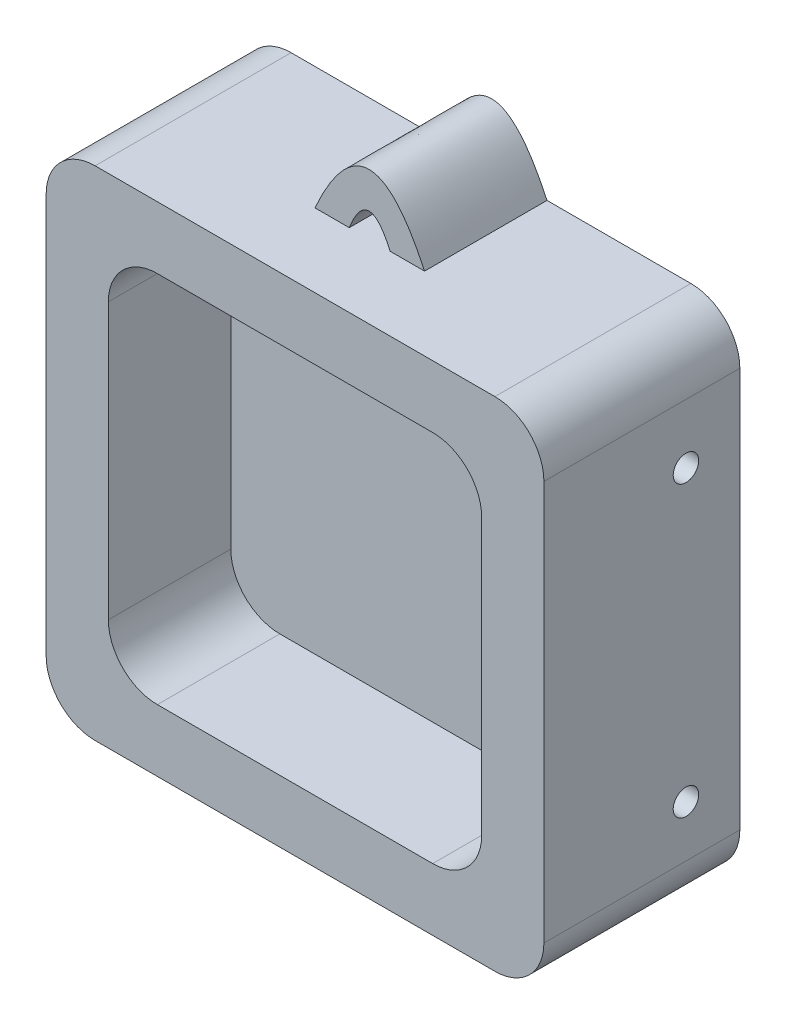
SolidWorks part; units mm, degrees
ref_plane "Front Plane" through (0, 0, 0) normal (0, 0, 1) x (1, 0, 0)
ref_plane "Top Plane" through (0, 0, 0) normal (0, 1, 0) x (1, 0, 0)
ref_plane "Right Plane" through (0, 0, 0) normal (1, 0, 0) x (0, 0, -1)
sketch "Sketch1" plane through (0, 0, 0) normal (0, 0, 1) x (1, 0, 0)
  line L1 (0, 0) -> (101.6, 0)
  line L2 (0, 0) -> (0, 101.6)
  line L3 (0, 101.6) -> (101.6, 101.6)
  line L4 (101.6, 0) -> (101.6, 101.6)
  line L5 (12.7, 88.9) -> (88.9, 88.9)
  line L6 (12.7, 88.9) -> (12.7, 12.7)
  line L7 (12.7, 12.7) -> (88.9, 12.7)
  line L8 (88.9, 88.9) -> (88.9, 12.7)
  spline S0 degree 2 poles (39.8729, 101.6) (50.7754, 126.2259) (62.2378, 101.6) knots 0 0 0 1 1 1
  spline S1 degree 2 poles (46.8729, 101.6) (50.757, 111.505) (55.2378, 101.6) knots 0 0 0 1 1 1
  dimension "D1" = 101.6
  dimension "D2" = 101.6
  dimension "D3" = 12.7
  dimension "D4" = 12.7
  dimension "D5" = 12.7
  dimension "D6" = 12.7
  dimension "D7" = 7
  dimension "D8" = 7
extrude "side" add sketch "Sketch1" along normal blind 40 contours L1 L4 L3 L2 L5 L8 L7 L6 region at (1.4368, 50.8, 0)
extrude "bottom " add sketch "Sketch1<8>" along normal blind 15 contours L8 L5 L6 L7 region at (50.8, 50.8, 0)
sketch "Sketch1<8>" plane through (0, 0, 0) normal (0, 0, 1) x (1, 0, 0) same geometry as "Sketch1"
extrude "holder" add sketch "Sketch1<10>" along normal blind 25 contours L3 S1 S0 region at (51, 107.0465, 0)
sketch "Sketch1<10>" plane through (0, 0, 0) normal (0, 0, 1) x (1, 0, 0) same geometry as "Sketch1"
fillet "Fillet1" radius 10 1 edges at (0, 101.6, 20)
fillet "Fillet2" radius 10 1 edges at (0, 0, 20)
fillet "Fillet3" radius 10 1 edges at (101.6, 0, 20)
fillet "Fillet4" radius 10 1 edges at (101.6, 101.6, 20)
sketch "Sketch2" plane through (101.6, 0, 0) normal (1, 0, 0) x (0, 0, -1)
  line L0 (0, 10) -> (0, 91.6) construction
  circle A0 centre (-11, 79.4963) radius 2.6
  circle A1 centre (-11, 20.4781) radius 2.6
  dimension "D1" = 5.2
  dimension "D2" = 5.2
  dimension "D3" = 11
  dimension "D4" = 11
extrude "Cut-Extrude1" cut sketch "Sketch2" against normal through all
fillet "Fillet5" radius 10 1 edges at (12.7, 88.9, 27.5)
fillet "Fillet6" radius 10 1 edges at (88.9, 88.9, 27.5)
fillet "Fillet7" radius 10 1 edges at (12.7, 12.7, 27.5)
fillet "Fillet8" radius 10 1 edges at (88.9, 12.7, 27.5)
